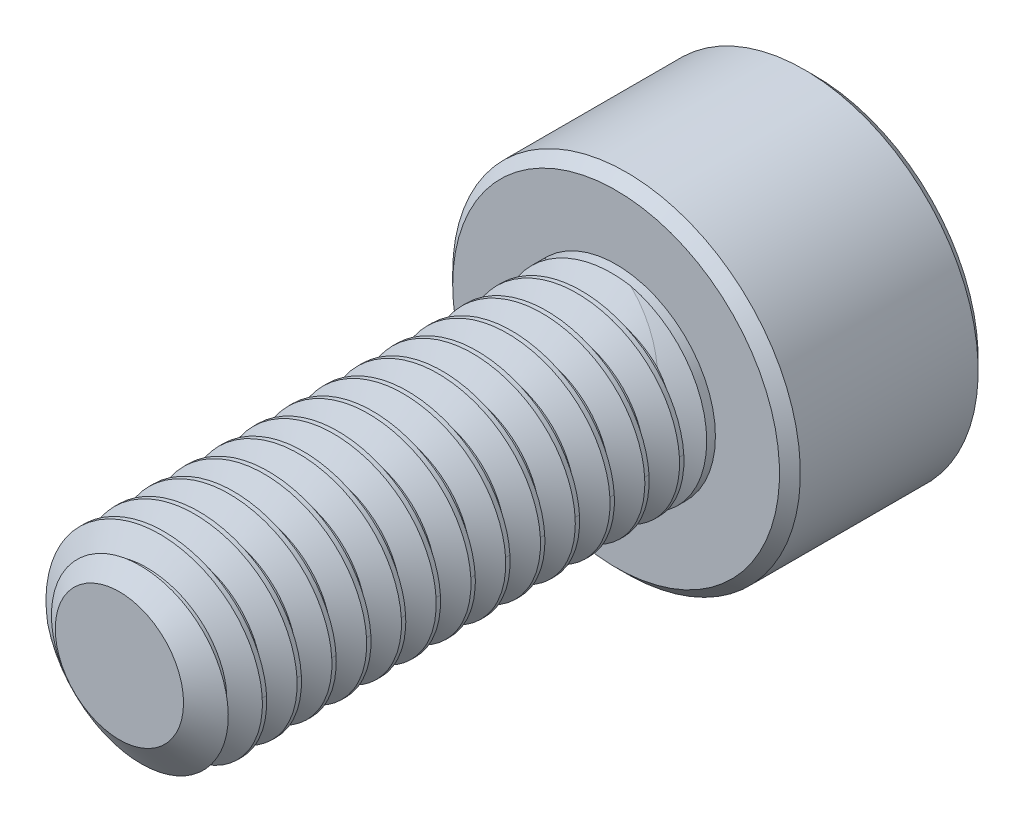
SolidWorks part; units mm, degrees
material "Alloy Steel"
ref_plane "Front Plane" through (0, 0, 0) normal (0, 0, 1) x (1, 0, 0)
ref_plane "Top Plane" through (0, 0, 0) normal (0, 1, 0) x (1, 0, 0)
ref_plane "Right Plane" through (0, 0, 0) normal (1, 0, 0) x (0, 0, -1)
sketch "Sketch1" plane through (0, 0, 0) normal (0, 0, 1) x (1, 0, 0)
  circle A0 centre (0, 0) radius 2
  dimension "OD" = 4
extrude "Extrude1" add sketch "Sketch1" against normal blind 10
sketch "Sketch2" plane through (0, 0, 0) normal (0, 0, 1) x (1, 0, 0)
  circle A0 centre (0, 0) radius 2 construction
  circle A1 centre (0, 0) radius 2
curve "Helix/Spiral1" pitch 0.7 height 10.7 radius 2 centre (0, 0, 0) axis (0, 0, -1) start towards (0, 1, 0) parameters "pitch"=0.7
sketch "Sketch3" plane through (0, 0, 0) normal (1, 0, 0) x (0, 0, -1)
  line L0 (-0.6125, 2) -> (-0.35, 1.5453)
  line L1 (-0.35, 1.5453) -> (-0.2625, 1.5453)
  line L2 (-0.2625, 1.5453) -> (0, 2)
  line L3 (-0.6125, 2) -> (0, 2)
  line L4 (-0.3063, 2) -> (-0.3063, 1.5453) construction
  line L5 (-0.4813, 1.7727) -> (-0.1313, 1.7727) construction
  line L6 (0, 2) -> (0, -2) construction
  line L7 (0, -2) -> (10, -2) construction
  point P11 (3.15, -2)
  dimension "D1" = 0.0875
  dimension "D2" = 0.35
  dimension "D3" = 60
  dimension "D4" = 3.15
sweep "Cut-Sweep1" cut profiles "Sketch3" path "Helix/Spiral1" align with end faces yes
sketch "Sketch4" plane through (0, 0, 0) normal (1, 0, 0) x (0, 0, -1)
  line L0 (0.4962, 2) -> (0, 1.2913)
  line L1 (0, 1.2913) -> (0, 2)
  line L2 (0.4962, 2) -> (0, 2)
  line L3 (-0.6125, 2) -> (0, 2) construction
  line L4 (0, 0) -> (7.0209, 0) construction
  dimension "D1" = 55
  dimension "D2" = 0.254
revolve "Cut-Revolve1" cut sketch "Sketch4" angle 360 about L4
sketch "Sketch5" plane through (0, 0, 0) normal (1, 0, 0) x (0, 0, -1)
  line L0 (10, 0.3311) -> (10, 1.814) construction
  line L1 (10, 2) -> (0.1203, 2)
  line L2 (10, 2) -> (10, 0)
  line L3 (10, 0) -> (0.0001, 0)
  line L4 (0.0001, 1.6698) -> (0.0001, 0)
  line L5 (0.1203, 2) -> (0.0001, 1.6698)
  line L6 (0, 0) -> (9.9695, 0) construction
  point P3 (0.0001, 2)
  point P10 (0.0001, 2)
  dimension "D1" = 0.3302
  dimension "Thread min" = 0.0001
  dimension "D3" = 20
revolve "partially thread" [suppressed] add sketch "Sketch5" angle 360 about L6
sketch "Sketch6" plane through (0, 0, -10) normal (0, 0, -1) x (-1, 0, 0)
  circle A0 centre (0, 0) radius 3.5
  dimension "head dia" = 7
extrude "Extrude2" add sketch "Sketch6" along normal blind 4
sketch "Sketch7" plane through (0, 0, -14) normal (0, 0, -1) x (-1, 0, 0)
  line L1 (0, 1.7321) -> (-1.5, 0.866)
  line L2 (-1.5, 0.866) -> (-1.5, -0.866)
  line L3 (-1.5, -0.866) -> (0, -1.7321)
  line L4 (0, -1.7321) -> (1.5, -0.866)
  line L5 (1.5, -0.866) -> (1.5, 0.866)
  line L6 (1.5, 0.866) -> (0, 1.7321)
  circle A0 centre (0, 0) radius 1.5 construction
  dimension "hex dia" = 3
extrude "Cut-Extrude1" cut sketch "Sketch7" against normal blind 2.25
sketch "Sketch8" plane through (0, 0, -14) normal (0, 0, -1) x (-1, 0, 0)
  circle A0 centre (0, 0) radius 1.7321
extrude "Cut-Extrude2" cut sketch "Sketch8" against normal through all draft 45
chamfer "Chamfer1" distance 0.21 angle 45 2 edges at (-3.5, 0, -14) (-3.5, 0, -10)
sketch "Sketch9" plane through (0, 0, 0) normal (1, 0, 0) x (0, 0, -1)
  line L0 (0, 2) -> (0, -2) construction
  line L1 (3.85, 2) -> (3.85, -2) construction
  dimension "D1" = 3.85
sketch "Sketch10" plane through (0, 0, 0) normal (1, 0, 0) x (0, 0, -1)
  line L0 (10, 2) -> (10, 0)
  line L1 (10, 2) -> (9.825, 2)
  line L2 (9.825, 2) -> (8.9966, 0)
  line L3 (10, 0) -> (8.9966, 0)
  line L4 (10, 3.29) -> (10, -3.29) construction
  dimension "D1" = 22.5
  dimension "D2" = 0.175
revolve "Revolve1" add sketch "Sketch10" angle 360 about L3
equation "\"D3@Helix/Spiral1\" = \"screw length@Extrude1\"+\"pitch@Helix/Spiral1\""
equation "\"D1@Sketch3\" = \"pitch@Helix/Spiral1\"*.125"
equation "\"D2@Sketch3\" = \"pitch@Helix/Spiral1\"*.5"
equation "\"D1@Cut-Extrude1\" = \"hex dia@Sketch7\"*.75"
equation "\"D1@Chamfer1\" = \"head dia@Sketch6\"*.03"
equation "\"D1@Sketch9\" = \"pitch@Helix/Spiral1\"*5.5"
equation "\"D2@Sketch10\" = \"pitch@Helix/Spiral1\"*.25"
equation "\"D4@Sketch3\" = \"pitch@Helix/Spiral1\"*4.50"
